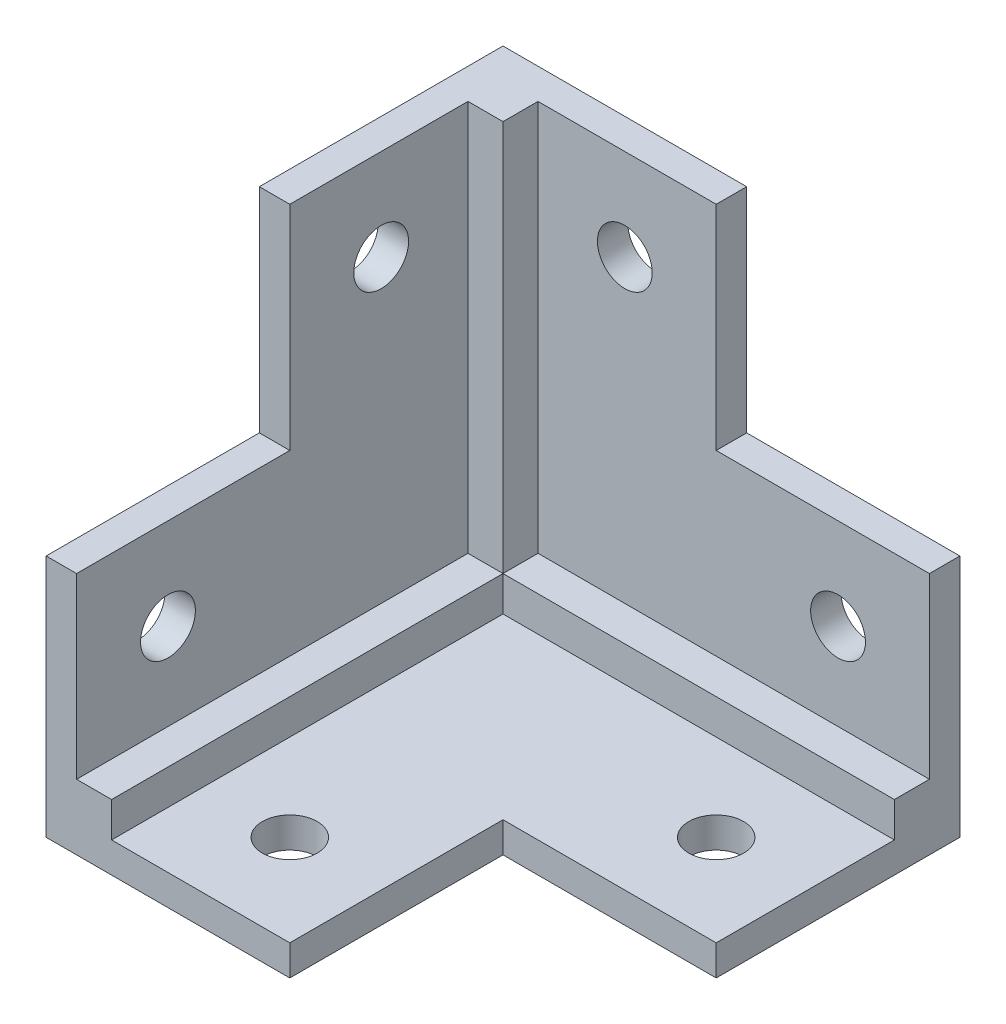
SolidWorks part; units mm, degrees
ref_plane "Front Plane" through (0, 0, 0) normal (0, 0, 1) x (1, 0, 0)
ref_plane "Top Plane" through (0, 0, 0) normal (0, 1, 0) x (1, 0, 0)
ref_plane "Right Plane" through (0, 0, 0) normal (1, 0, 0) x (0, 0, -1)
sketch "Sketch2" plane through (0, 0, 0) normal (0, 0, 1) x (1, 0, 0)
  line L1 (0, 0) -> (38.1, 0)
  line L2 (0, 0) -> (0, 38.1)
  line L3 (0, 38.1) -> (38.1, 38.1)
  line L4 (38.1, 0) -> (38.1, 38.1)
  dimension "D1" = 38.1
  dimension "D2" = 38.1
extrude "Boss-Extrude2" add sketch "Sketch2" along normal blind 38.1
sketch "Sketch3" plane through (0, 0, 38.1) normal (0, 0, 1) x (1, 0, 0)
  line L0 (0, 0) -> (38.1, 0) construction
  line L1 (38.1, 38.1) -> (2.54, 38.1)
  line L2 (38.1, 38.1) -> (38.1, 2.54)
  line L3 (38.1, 2.54) -> (2.54, 2.54)
  line L4 (2.54, 38.1) -> (2.54, 2.54)
  line L5 (0, 38.1) -> (0, 0) construction
  dimension "D1" = 2.54
  dimension "D2" = 2.54
extrude "Cut-Extrude1" cut sketch "Sketch3" against normal blind 35.56
sketch "Sketch4" plane through (0, 0, 2.54) normal (0, 0, 1) x (1, 0, 0)
  line L1 (38.1, 38.1) -> (20.32, 38.1)
  line L2 (38.1, 38.1) -> (38.1, 20.32)
  line L3 (38.1, 20.32) -> (20.32, 20.32)
  line L4 (20.32, 38.1) -> (20.32, 20.32)
  line L6 (38.1, 38.1) -> (2.54, 38.1) construction
  line L7 (38.1, 2.54) -> (38.1, 38.1) construction
  line L8 (2.54, 38.1) -> (2.54, 2.54) construction
  line L9 (2.54, 2.54) -> (38.1, 2.54) construction
  circle A0 centre (12.7, 30.48) radius 2.286
  circle A1 centre (30.48, 12.7) radius 2.286
  dimension "D4" = 7.62
  dimension "D5" = 4.572
  dimension "D1" = 17.78
  dimension "D2" = 17.78
  dimension "D3" = 7.62
  dimension "D6" = 7.62
  dimension "D7" = 7.62
extrude "Cut-Extrude2" cut sketch "Sketch4" against normal through all
sketch "Sketch5" plane through (0, 2.54, 0) normal (0, 1, 0) x (1, 0, 0)
  line L1 (38.1, -38.1) -> (20.32, -38.1)
  line L2 (38.1, -38.1) -> (38.1, -20.32)
  line L3 (38.1, -20.32) -> (20.32, -20.32)
  line L4 (20.32, -38.1) -> (20.32, -20.32)
  line L5 (2.54, -2.54) -> (2.54, -38.1) construction
  line L8 (38.1, -2.54) -> (38.1, -38.1) construction
  line L9 (2.54, -38.1) -> (38.1, -38.1) construction
  line L10 (2.54, -2.54) -> (38.1, -2.54) construction
  circle A0 centre (30.48, -12.7) radius 2.286
  circle A1 centre (12.7, -30.48) radius 2.286
  point P18 (0, 0)
  dimension "D1" = 4.572
  dimension "D2" = 7.62
  dimension "D3" = 7.62
  dimension "D4" = 17.78
  dimension "D5" = 17.78
  dimension "D6" = 7.62
  dimension "D7" = 7.62
extrude "Cut-Extrude3" cut sketch "Sketch5" against normal through all
sketch "Sketch6" plane through (2.54, 0, 0) normal (1, 0, 0) x (0, 0, -1)
  line L1 (-38.1, 38.1) -> (-20.32, 38.1)
  line L2 (-38.1, 38.1) -> (-38.1, 20.32)
  line L3 (-38.1, 20.32) -> (-20.32, 20.32)
  line L4 (-20.32, 38.1) -> (-20.32, 20.32)
  line L7 (-2.54, 38.1) -> (-2.54, 20.32) construction
  line L8 (-20.32, 2.54) -> (-38.1, 2.54) construction
  line L9 (-38.1, 38.1) -> (-38.1, 2.54) construction
  line L10 (-2.54, 38.1) -> (-38.1, 38.1) construction
  circle A0 centre (-12.7, 30.48) radius 2.286
  circle A1 centre (-30.48, 12.7) radius 2.286
  point P11 (0, 0)
  point P18 (0, 0)
  point P22 (0, 0)
  dimension "D1" = 4.572
  dimension "D2" = 17.78
  dimension "D3" = 17.78
  dimension "D4" = 7.62
  dimension "D5" = 7.62
  dimension "D6" = 7.62
  dimension "D7" = 7.62
extrude "Cut-Extrude4" cut sketch "Sketch6" against normal through all
sketch "Sketch7" plane through (0, 2.54, 0) normal (0, 1, 0) x (1, 0, 0)
  line L0 (2.54, -38.1) -> (2.54, -2.54)
  line L1 (2.54, -2.54) -> (38.1, -2.54)
  line L2 (38.1, -2.54) -> (38.1, -5.461)
  line L3 (38.1, -2.54) -> (38.1, -20.32) construction
  line L4 (38.1, -5.461) -> (5.461, -5.461)
  line L5 (5.461, -5.461) -> (5.461, -38.1)
  line L6 (2.54, -38.1) -> (20.32, -38.1) construction
  line L7 (5.461, -38.1) -> (2.54, -38.1)
  dimension "D1" = 2.921
  dimension "D2" = 2.921
extrude "Boss-Extrude3" add sketch "Sketch7" along normal blind 2.921
sketch "Sketch8" plane through (0, 5.461, 0) normal (0, 1, 0) x (1, 0, 0)
  line L1 (5.461, -5.461) -> (2.54, -5.461)
  line L2 (5.461, -5.461) -> (5.461, -2.54)
  line L3 (5.461, -2.54) -> (2.54, -2.54)
  line L4 (2.54, -5.461) -> (2.54, -2.54)
extrude "Boss-Extrude4" add sketch "Sketch8" along normal up to surface (32.639 mm away) up to face at (7.62, 38.1, 7.62)
